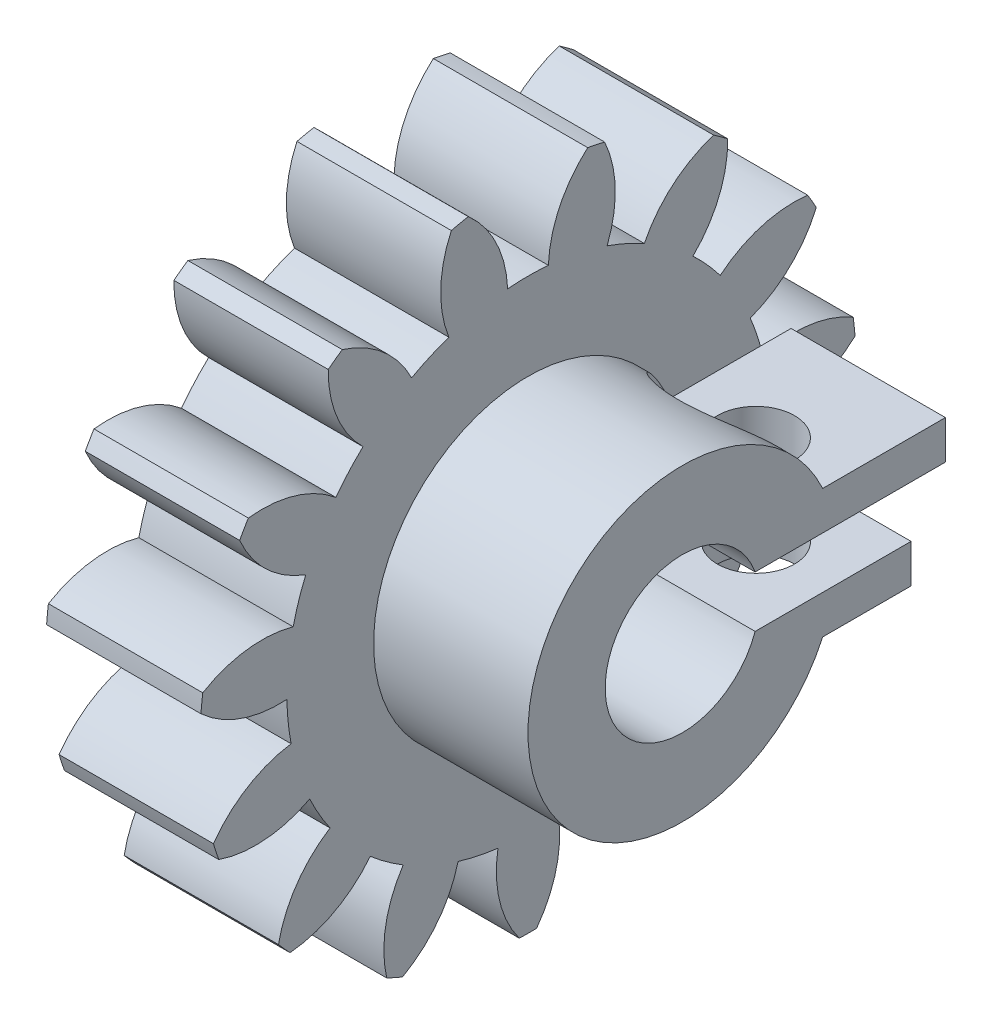
SolidWorks part; units mm, degrees
ref_plane "Plane1" through (0, 0, 0) normal (0, 0, 1) x (1, 0, 0)
ref_plane "Plane2" through (0, 0, 0) normal (0, 1, 0) x (1, 0, 0)
ref_plane "Plane3" through (0, 0, 0) normal (1, 0, 0) x (0, 0, -1)
sketch "HoldingSke" plane through (0, 0, 0) normal (0, 1, 0) x (1, 0, 0)
  line L0 (0, 0) -> (0.644, -0.1725)
  line L1 (-15, 0) -> (100, 0) construction
  line L2 (0, 0) -> (-2.1039, 2.3779)
  line L3 (0, 0) -> (-11.863, 4.5341)
  line L4 (0, 0) -> (8.3417, 2.2352)
  line L5 (0, 0) -> (-46.8476, -17.4728)
  line L6 (0, 0) -> (-4.9738, -3.3558)
  line L7 (-2.1039, 2.3779) -> (8.6586, 51.2059)
  line L8 (-76.2, 54.61) -> (-75.2, 54.61)
  line L9 (-71.009, 38.7566) -> (-53.1078, 45.2721)
  line L10 (-76.2, 71.12) -> (104.1128, 71.12)
  line L11 (0, 0) -> (-6, 0)
  line L12 (-76.2, 101.6) -> (-76.147, 101.6)
  line L13 (24.9733, 27.94) -> (52.9518, 28.4284)
  line L14 (24.9733, 27.94) -> (24.9743, 27.94)
  line L15 (24.9733, 27.94) -> (100.4006, 29.5858)
  line L16 (-63.627, -1.5) -> (-12.827, -1.5)
  circle A0 centre (0, 0) radius 3
  circle A1 centre (0, 0) radius 9.374
  circle A2 centre (0, 0) radius 37.5
  circle A3 centre (0, 0) radius 3
  dimension "Num_teeth" = 15
  dimension "Pitch_radius" = 180.3128
  dimension "Width" = 6
  dimension "Thickness" = 6
sketch "BasProSke" plane through (0, 0, 0) normal (0, 1, 0) x (1, 0, 0)
  line L0 (-10, 0) -> (60, 0) construction
  line L1 (0, 0) -> (0, 12.75)
  line L2 (0, 0) -> (6, 0)
  line L3 (6, 0) -> (6, 12.75)
  line L4 (6, 12.75) -> (0, 12.75)
  dimension "Thickness" = 6
  dimension "Diameter" = 25.5
revolve "Base-Revolve" add sketch "BasProSke" angle 360 about L0
sketch "TooCutSke" plane through (0, 0, 0) normal (1, 0, 0) x (0, 0, -1)
  line L1 (0, 0) -> (0, 107) construction
  line L2 (0, 0) -> (-1.2686, 11.1782) construction
  line L3 (0, 0) -> (-4.6563, 21.9061) construction
  line L4 (-1.2686, 11.1782) -> (-2.3281, 10.953) construction
  arc A0 (0.7915, 9.3405) -> (-0.7915, 9.3405) centre (0, 0) ccw
  arc A1 (2.3447, 12.5584) -> (-2.3447, 12.5584) centre (0, 0) ccw
  circle A2 centre (0, 0) radius 11.25 construction
  circle A3 centre (0, 0) radius 10.5715 construction
  arc A4 (-0.7915, 9.3405) -> (-2.3447, 12.5584) centre (-5.2877, 9.1541) ccw
  arc A5 (2.3447, 12.5584) -> (0.7915, 9.3405) centre (5.2877, 9.1541) ccw
extrude "ToothCut" cut sketch "TooCutSke" along normal through all
fillet "Breaks" [suppressed] radius 0.03 tangent propagation no
fillet "RootFillets" [suppressed] radius 0.376
pattern_circular "TeethCuts" count 15 every 24 about axis through (-10, 0, 0) along (1, 0, 0) of "ToothCut", "RootFillets", "Breaks"
sketch "HubNeaOneSke" plane through (0, 0, 0) normal (-1, 0, 0) x (0, 0, 1)
  circle A0 centre (0, 0) radius 9.374
  dimension "Diameter" = 18.748
extrude "HubNearOne" [suppressed] add sketch "HubNeaOneSke" along normal blind 44.0001
sketch "HubNeaBotSke" plane through (0, 0, 0) normal (-1, 0, 0) x (0, 0, 1)
  circle A0 centre (0, 0) radius 9.374
  dimension "Diameter" = 18.748
extrude "HubNearBoth" [suppressed] add sketch "HubNeaBotSke" along normal blind 22
ref_plane "FarPln" through (6, 0, 0) normal (1, 0, 0) x (0, 0, -1)
sketch "HubFarSke" plane through (6, 0, 0) normal (1, 0, 0) x (0, 0, -1)
  circle A0 centre (0, 0) radius 9.374
  dimension "Diameter" = 18.748
extrude "HubFar" [suppressed] add sketch "HubFarSke" along normal blind 22
sketch "BorSke" plane through (0, 0, 0) normal (1, 0, 0) x (0, 0, -1)
  circle A0 centre (0, 0) radius 3
  dimension "Diameter" = 6
extrude "Bore" cut sketch "BorSke" along normal mid plane 100.0001
sketch "KeySke" plane through (0, 0, 0) normal (1, 0, 0) x (0, 0, -1)
  line L0 (-1, 0) -> (-1, 4)
  line L1 (-1, 4) -> (1, 4)
  line L2 (1, 4) -> (1, 0)
  line L3 (0, 0) -> (0, 34) construction
  line L4 (-1, 0) -> (1, 0)
  dimension "Width" = 2
extrude "Keyway" [suppressed] cut sketch "KeySke" along normal mid plane 100.0001
pattern_circular "Keyway2" [suppressed] count 2 every 90 about axis through (-10, 0, 0) along (1, 0, 0) reverse direction yes
sketch "Sketch1" plane through (6, 0, 0) normal (1, 0, 0) x (0, 0, -1)
  line L0 (-8.9706, 0) -> (4.6808, 0) construction
  circle A0 centre (0, 0) radius 3
  circle A2 centre (0, 0) radius 6
  point P12 (0, 0)
  dimension "D1" = 12
extrude "Boss-Extrude2" add sketch "Sketch1" along normal blind 6
sketch "Sketch2" plane through (12, 0, 0) normal (1, 0, 0) x (0, 0, -1)
  line L1 (1.8125, 1) -> (7.0934, 1)
  line L2 (1.8125, 1) -> (1.8125, -1)
  line L3 (1.8125, -1) -> (7.0934, -1)
  line L4 (7.0934, 1) -> (7.0934, -1)
  line L5 (1.8125, 1) -> (7.0934, -1) construction
  line L6 (1.8125, -1) -> (7.0934, 1) construction
  point P0 (4.453, 0)
  point P5 (4.453, 0)
  dimension "D1" = 2
extrude "Cut-Extrude1" cut sketch "Sketch2" against normal up to surface (6 mm away) up to face at (6, 0, 0)
sketch "Sketch3" plane through (0, -1, 0) normal (0, 1, 0) x (1, 0, 0)
  line L0 (12, 2.8284) -> (12, 5.9161) construction
  line L1 (6, 2.8284) -> (12, 2.8284)
  line L2 (6, 2.8284) -> (6, 8.8895)
  line L3 (6, 8.8895) -> (12, 8.8895)
  line L4 (12, 2.8284) -> (12, 8.8895)
  point P5 (12, 2.8284)
extrude "Boss-Extrude3" add sketch "Sketch3" against normal blind 1.5
sketch "Sketch5" plane through (0, 1, 0) normal (0, -1, 0) x (1, 0, 0)
  line L0 (6, -10.2244) -> (6, -9.3205) construction
  line L1 (6, -2.8284) -> (12, -2.8284) construction
  line L2 (6, -2.8284) -> (6, -9.3205) construction
  line L3 (12, -10.2244) -> (6, -10.2244) construction
  line L4 (12, -2.8284) -> (12, -10.2244) construction
  line L5 (6, -10.2244) -> (6, -9.3205)
  line L6 (6, -2.8284) -> (12, -2.8284)
  line L7 (6, -2.8284) -> (6, -9.3205)
  line L8 (12, -10.2244) -> (6, -10.2244)
  line L9 (12, -2.8284) -> (12, -10.2244)
extrude "Boss-Extrude4" add sketch "Sketch5" against normal blind 1.5
sketch "Sketch6" plane through (0, -1, 0) normal (0, 1, 0) x (1, 0, 0)
  line L0 (12, 2.8284) -> (12, 8.8895) construction
  line L1 (12, 8.8895) -> (6, 8.8895) construction
  circle A0 centre (9, 5.859) radius 1.5
  point P0 (0, 0)
  point P3 (12, 5.859)
  point P4 (9.1304, 5.8163)
  point P7 (9, 8.8895)
  dimension "D1" = 3
extrude "Cut-Extrude2" cut sketch "Sketch6" against normal through all both and the other way through all
sketch "Sketch7" plane through (0, 2.5, 0) normal (0, 1, 0) x (1, 0, 0)
  arc A5 (6.1112, 5.0497) -> (11.8888, 5.0497) centre (9, 5.859) ccw
  arc A6 (11.8888, 5.0497) -> (6.1112, 5.0497) centre (9, 5.859) ccw
  arc A7 (6.1112, 5.0497) -> (11.8888, 5.0497) centre (9, 5.859) ccw
  arc A8 (11.8888, 5.0497) -> (6.1112, 5.0497) centre (9, 5.859) ccw
  dimension "D1" = 1.5
extrude "Cut-Extrude3" cut sketch "Sketch7" along normal through all
equation "' \"Module@HoldingSke\" = 6.35"
equation "' \"Num_teeth@HoldingSke\" = 12"
equation "' \"Ap@HoldingSke\" =  20"
equation "' \"Ap@HoldingSke\" = 20"
equation "' \"Width@HoldingSke\" = 0.5 * 25.4"
equation "' \"Hub_dia@HoldingSke\"= 1 * 25.4"
equation "' \"Hub_dia@HoldingSke\" = 1 * 25.4"
equation "' \"Overall_len@HoldingSke\" = 1.0 * 25.4"
equation "' \"Bore@HoldingSke\" = 0.75 * 25.4"
equation "' \"T_dim@HoldingSke\" = 0.1 * 25.4"
equation "' \"Width@KeySke\" = 0.25 * 25.4"
equation "' \"Show_teeth@HoldingSke\" = 13"
equation "' \"Backlash@HoldingSke\" = 0.009 * 25.4"
equation "' \"Addendum_fac@HoldingSke\" = 1.0"
equation "' \"Dedendum_fac@HoldingSke\" = 1.25"
equation "' \"Dedendum_add@HoldingSke\" = 0.00005 * 25.4"
equation "' \"Clearance_fac@HoldingSke\" = 0.25"
equation "\"Pitch@HoldingSke\" = 1 / \"Module@HoldingSke\""
equation "\"Overcut_dia@TooCutSke\" = (\"Num_teeth@HoldingSke\" + 2 * \"Addendum_fac@HoldingSke\") / \"Pitch@HoldingSke\" + 0.002 * 25.4"
equation "\"Pitch_dia@TooCutSke\" = \"Num_teeth@HoldingSke\" / \"Pitch@HoldingSke\""
equation "\"Base_dia@TooCutSke\" = \"Num_teeth@HoldingSke\" / \"Pitch@HoldingSke\" * cos((\"Ap@HoldingSke\"  * 3.14159265 / 180))"
equation "\"Root_dia@TooCutSke\" = (\"Num_teeth@HoldingSke\" + 2) / \"Pitch@HoldingSke\" - 2 * (\"Addendum_fac@HoldingSke\" + \"Dedendum_fac@HoldingSke\") / \"Pitch@HoldingSke\" - \"Dedendum_add@HoldingSke\" * 2"
equation "\"Half_ang@TooCutSke\" = 180 / \"Num_teeth@HoldingSke\""
equation "\"Half_CT@TooCutSke\" = \"Num_teeth@HoldingSke\" / \"Pitch@HoldingSke\" * sin((3.14159265 / 2 / \"Num_teeth@HoldingSke\")) / 2 - 7 * \"Backlash@HoldingSke\" / 4"
equation "\"Flank_rad@TooCutSke\" = \"Num_teeth@HoldingSke\" / \"Pitch@HoldingSke\" / 5"
equation "\"Radius@RootFillets\" = \"Clearance_fac@HoldingSke\" / \"Pitch@HoldingSke\" + \"Dedendum_add@HoldingSke\""
equation "\"Break_rad@Breaks\" = 0.02 / \"Pitch@HoldingSke\""
equation "\"Thickness@HoldingSke\" = \"Width@HoldingSke\""
equation "\"OAL@HoldingSke\" = \"Thickness@HoldingSke\""
equation "\"MHD@HoldingSke\" = (\"Num_teeth@HoldingSke\" + 2) / \"Pitch@HoldingSke\" - 2 * (\"Addendum_fac@HoldingSke\" + \"Dedendum_fac@HoldingSke\")  / \"Pitch@HoldingSke\" - \"Dedendum_add@HoldingSke\" * 2"
equation "\"MBD@HoldingSke\" = (\"Num_teeth@HoldingSke\" + 2) / \"Pitch@HoldingSke\" - 2 * (\"Addendum_fac@HoldingSke\" + \"Dedendum_fac@HoldingSke\")  / \"Pitch@HoldingSke\" - \"Dedendum_add@HoldingSke\" * 2 - 0.002 * 25.4"
equation "\"MHD@HoldingSke\" = ((sgn( \"MHD@HoldingSke\" - \"Hub_dia@HoldingSke\" )-1)*( \"MHD@HoldingSke\" - \"Hub_dia@HoldingSke\" ))/-2+ \"Hub_dia@HoldingSke\""
equation "\"MBD@HoldingSke\" = ((sgn( \"MBD@HoldingSke\" - \"Bore@HoldingSke\" )-1)*( \"MBD@HoldingSke\" - \"Bore@HoldingSke\" ))/-2+ \"Bore@HoldingSke\""
equation "\"OAL@HoldingSke\" = ((sgn( \"OAL@HoldingSke\" - \"Overall_len@HoldingSke\" )+1)*( \"OAL@HoldingSke\" - \"Overall_len@HoldingSke\" ))/2 + \"Overall_len@HoldingSke\" + 0.000002 * 25.4"
equation "\"Num_teeth@TeethCuts\" = int( \"Show_teeth@HoldingSke\" ) + 1"
equation "\"Num_teeth@TeethCuts\" = ((sgn( \"Num_teeth@TeethCuts\" - \"Num_teeth@HoldingSke\" )-1)*( \"Num_teeth@TeethCuts\" - \"Num_teeth@HoldingSke\" ))/-2+ \"Num_teeth@HoldingSke\""
equation "\"Num_teeth@TeethCuts\" = ((sgn( \"Num_teeth@TeethCuts\" - 2.0)+1)*( \"Num_teeth@TeethCuts\" - 2.0))/2 +2.0"
equation "\"Angle@TeethCuts\" = 360.0 / \"Num_teeth@HoldingSke\""
equation "\"Diameter@BasProSke\" = (\"Num_teeth@HoldingSke\" + 2 * \"Addendum_fac@HoldingSke\") / \"Pitch@HoldingSke\""
equation "\"Thickness@BasProSke\"  = \"Thickness@HoldingSke\""
equation "' \"Fillet_rad@BasProSke\" =  \"Thickness@HoldingSke\" * 0.05"
equation "' \"Fillet_rad@BasProSke\" = \"Thickness@HoldingSke\" * 0.05"
equation "\"MHD@HoldingSke\" = ((sgn( \"MHD@HoldingSke\" - \"Root_dia@TooCutSke\" )-1)*( \"MHD@HoldingSke\" - \"Root_dia@TooCutSke\" ))/-2+ \"Root_dia@TooCutSke\""
equation "\"Diameter@HubNeaOneSke\" = \"MHD@HoldingSke\""
equation "\"Length@HubNearOne\" = \"OAL@HoldingSke\" - \"Thickness@BasProSke\""
equation "\"Diameter@HubNeaBotSke\" = \"MHD@HoldingSke\""
equation "\"Length@HubNearBoth\" = ( \"OAL@HoldingSke\" - \"Thickness@BasProSke\" ) / 2.0"
equation "\"Thickness@FarPln\" = \"Thickness@BasProSke\""
equation "\"Diameter@HubFarSke\" = \"MHD@HoldingSke\""
equation "\"Length@HubFar\" = ( \"OAL@HoldingSke\" - \"Thickness@BasProSke\" ) / 2.0"
equation "\"Diameter@BorSke\" = \"MBD@HoldingSke\""
equation "\"D1@Bore\" = \"OAL@HoldingSke\" * 2.0"
equation "\"D1@Keyway\" = \"OAL@HoldingSke\" * 2.0"
equation "\"Offset@KeySke\" = \"T_dim@HoldingSke\" + \"MBD@HoldingSke\" / 2.0"
